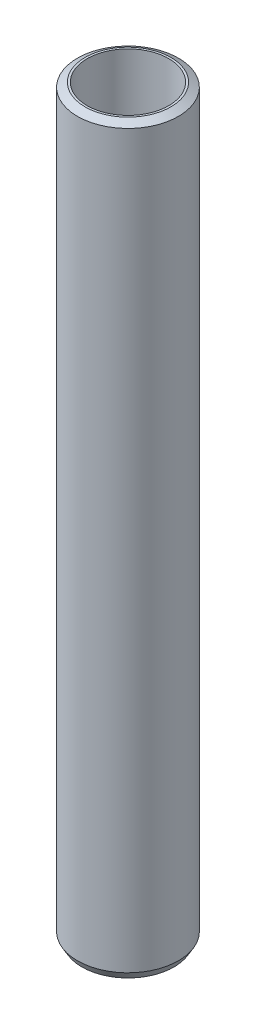
SolidWorks part; units mm, degrees
ref_plane "Front Plane" through (0, 0, 0) normal (0, 0, 1) x (1, 0, 0)
ref_plane "Top Plane" through (0, 0, 0) normal (0, 1, 0) x (1, 0, 0)
ref_plane "Right Plane" through (0, 0, 0) normal (1, 0, 0) x (0, 0, -1)
sketch "Sketch1" plane through (0, 0, 0) normal (0, 1, 0) x (1, 0, 0)
  circle A0 centre (0, 0) radius 22.5
  dimension "SHAFT_OD" = 45
extrude "Boss-Extrude1" add sketch "Sketch1" along normal blind 331.144
sketch "Sketch2" plane through (0, 0, 0) normal (0, 1, 0) x (1, 0, 0)
  circle A0 centre (0, 0) radius 18.1781
  dimension "BORE_D" = 36.3562
extrude "Cut-Extrude1" cut sketch "Sketch2" along normal through all
chamfer "Chamfer1" distance 1.9592 angle 60 2 edges at (0, 331.144, 22.5) (0, 0, 22.5) first distance on face at (0, 331.144, 22.5) first distance on face at (0, 0, 18.1781)
